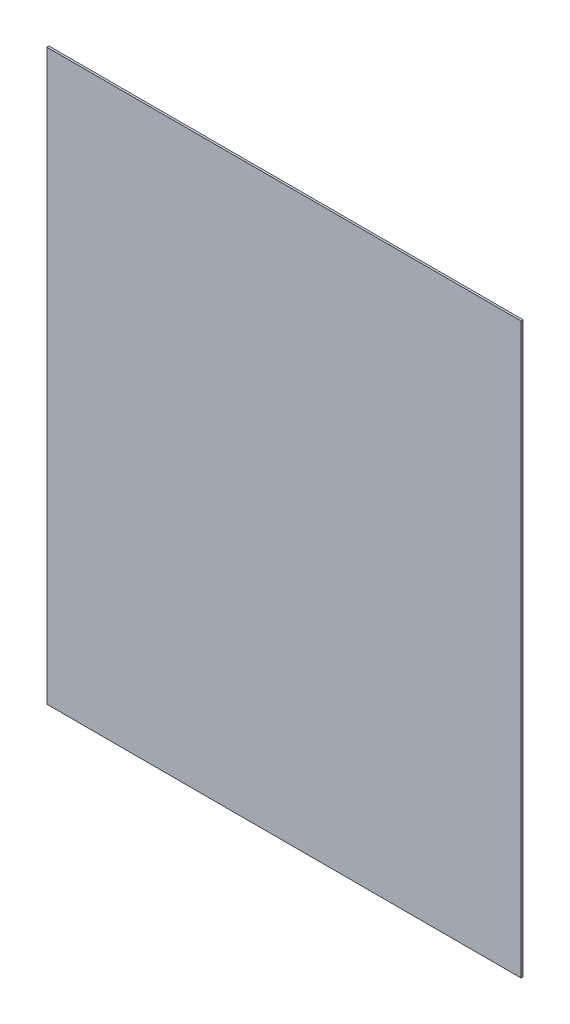
SolidWorks part; units mm, degrees
ref_plane "Front Plane" through (0, 0, 0) normal (0, 0, 1) x (1, 0, 0)
ref_plane "Top Plane" through (0, 0, 0) normal (0, 1, 0) x (1, 0, 0)
ref_plane "Right Plane" through (0, 0, 0) normal (1, 0, 0) x (0, 0, -1)
sketch "Sketch1" plane through (0, 0, 0) normal (0, 0, 1) x (1, 0, 0)
  line L0 (-812.8, 865.124) -> (-14.224, 865.124) construction
  line L1 (-26.924, 865.124) -> (-788.924, 865.124)
  line L2 (-26.924, 865.124) -> (-26.924, 1779.524)
  line L3 (-26.924, 1779.524) -> (-788.924, 1779.524)
  line L4 (-788.924, 865.124) -> (-788.924, 1779.524)
  line L5 (-14.224, 0) -> (-14.224, 865.124) construction
  dimension "D1" = 762
  dimension "D2" = 914.4
  dimension "D3" = 12.7
extrude "Boss-Extrude1" add sketch "Sketch1" against normal blind 3.302
